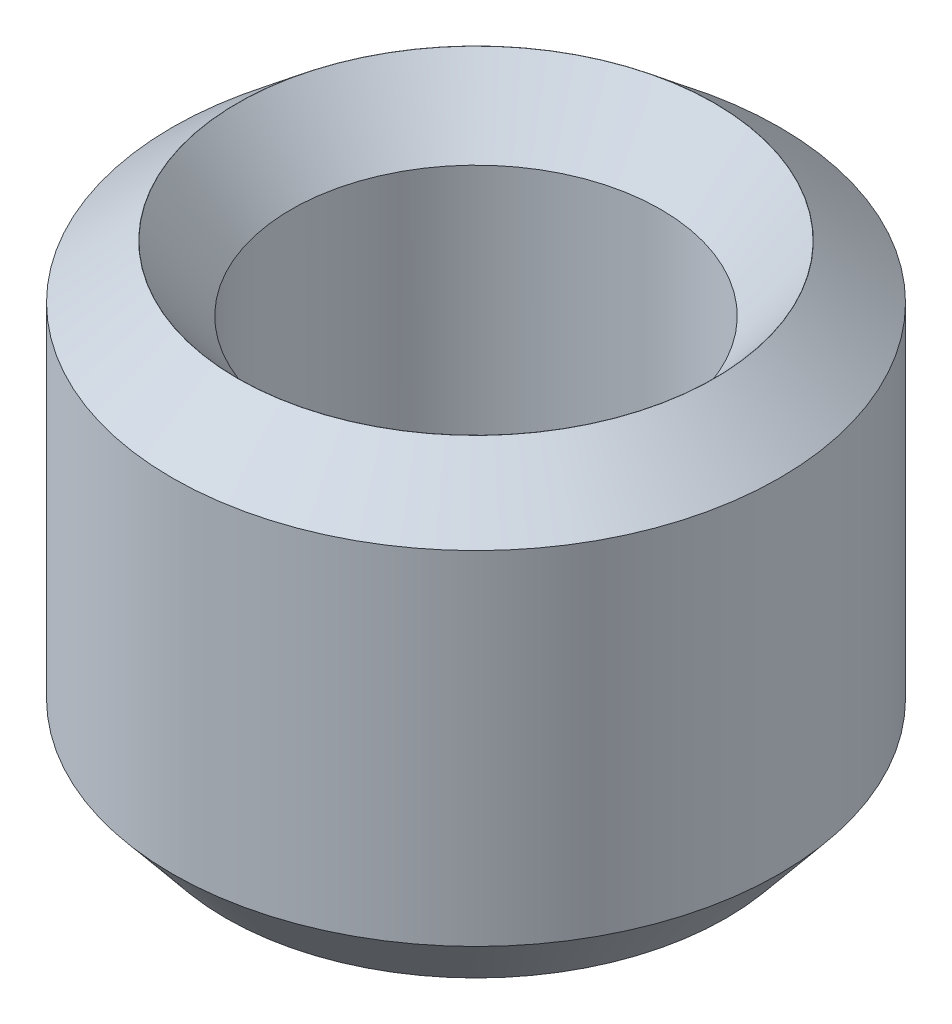
SolidWorks part; units mm, degrees
ref_plane "Front Plane" through (0, 0, 0) normal (0, 0, 1) x (1, 0, 0)
ref_plane "Top Plane" through (0, 0, 0) normal (0, 1, 0) x (1, 0, 0)
ref_plane "Right Plane" through (0, 0, 0) normal (1, 0, 0) x (0, 0, -1)
sketch "Sketch1" plane through (0, 0, 0) normal (0, 1, 0) x (1, 0, 0)
  circle A0 centre (0, 0) radius 10
  dimension "SLEEVE_OD" = 20
extrude "Boss-Extrude1" add sketch "Sketch1" along normal blind 15.2008
sketch "Sketch2" plane through (0, 0, 0) normal (0, 1, 0) x (1, 0, 0)
  circle A0 centre (0, 0) radius 6.0829
  dimension "BORE_D" = 12.1658
extrude "Cut-Extrude1" cut sketch "Sketch2" along normal through all
chamfer "Chamfer1" distance 1.7658 angle 50.561 4 edges at (0, 15.2008, 6.0829) (0, 0, 6.0829) (0, 0, 10) (0, 15.2008, 10) first distance on face at (0, 15.2008, 6.0829) first distance on face at (0, 0, 6.0829) first distance on face at (0, 15.2008, 10)
